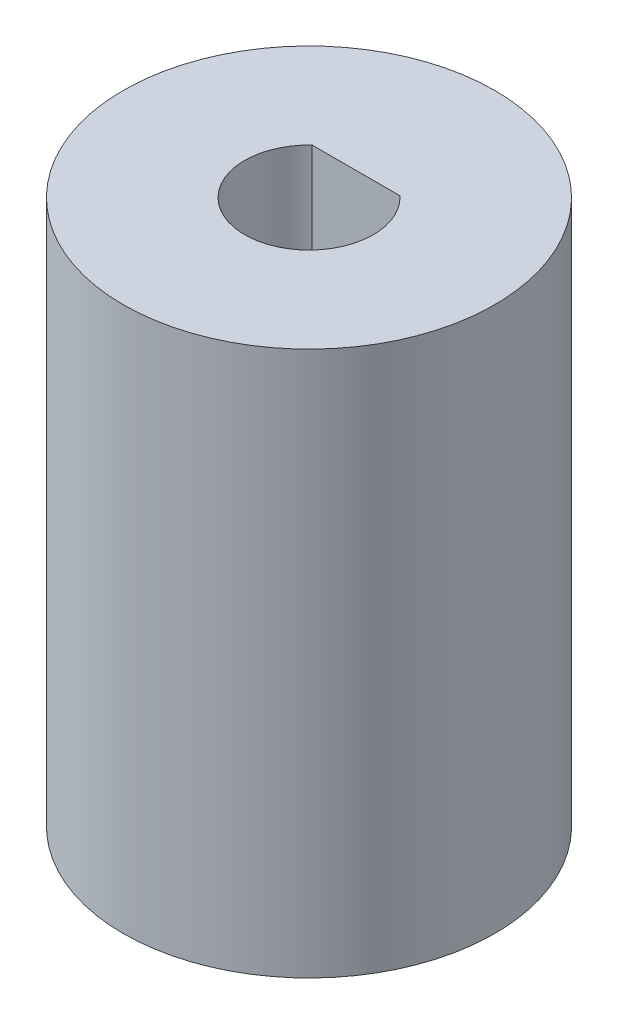
SolidWorks part; units mm, degrees
ref_plane "Front Plane" through (0, 0, 0) normal (0, 0, 1) x (1, 0, 0)
ref_plane "Top Plane" through (0, 0, 0) normal (0, 1, 0) x (1, 0, 0)
ref_plane "Right Plane" through (0, 0, 0) normal (1, 0, 0) x (0, 0, -1)
sketch "Sketch1" plane through (0, 0, 0) normal (0, 1, 0) x (1, 0, 0)
  circle A0 centre (0, 0) radius 4.7625
  circle A1 centre (0, 0) radius 7.5
  dimension "D1" = 9.525
  dimension "D2" = 15
extrude "Boss-Extrude1" add sketch "Sketch1" along normal blind 10 contours A1 A0 region at (-7.2879, 0, 0)
sketch "Sketch2" plane through (0, 10, 0) normal (0, 1, 0) x (1, 0, 0)
  circle A0 centre (0, 0) radius 4.7625 construction
  circle A1 centre (0, 0) radius 4.7625
  circle A3 centre (0, 0) radius 7.5
  circle A4 centre (0, 0) radius 7.5
  circle M1 centre (0, 0) radius 4.7625
  circle M2 centre (0, 0) radius 7.5
  dimension "D1" = 0
extrude "Boss-Extrude2" add sketch "Sketch2" along normal blind 2 contours M2 M1 | M1 region at (0, 10, 0) region at (-7.2879, 10, 0)
sketch "Sketch3" plane through (0, 12, 0) normal (0, 1, 0) x (1, 0, 0)
  circle A0 centre (0, 0) radius 2.6
  circle A1 centre (0, 0) radius 7.5
  dimension "D1" = 5.2
  dimension "D2" = 15
extrude "Boss-Extrude3" add sketch "Sketch3" along normal blind 10
chamfer "Chamfer1" [suppressed] distance 2.5 angle 45
sketch "Sketch4" plane through (0, 22, 0) normal (0, 1, 0) x (1, 0, 0)
  line L0 (-1.7748, 1.9) -> (1.7748, 1.9)
  circle A0 centre (0, 0) radius 2.6 construction
  circle A1 centre (0, 0) radius 2.6
  circle M2 centre (0, 0) radius 2.6
  dimension "D1" = 4.5
extrude "Boss-Extrude4" add sketch "Sketch4" against normal up to surface (10 mm away) contours L0 M2 region at (0, 22, -2.1835) up to face at (0, 12, 2.6)
